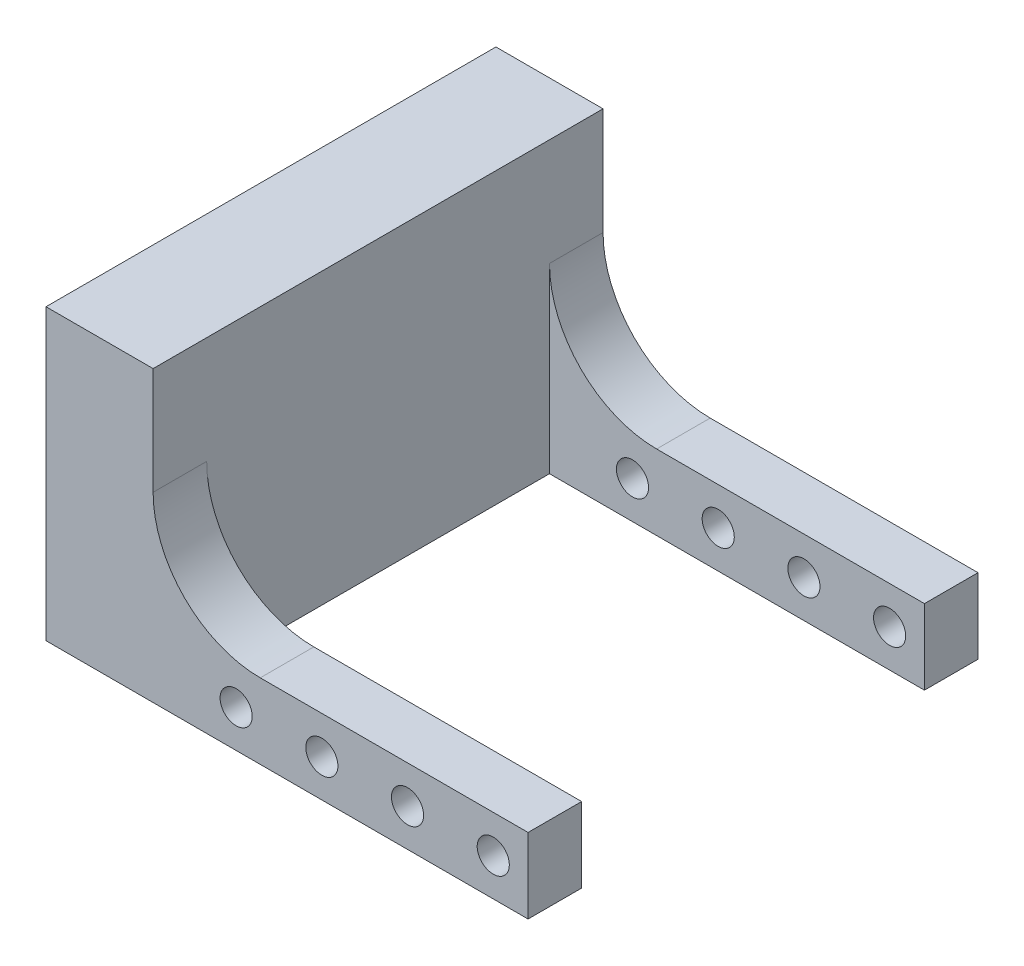
SolidWorks part; units mm, degrees
ref_plane "Plan de face" through (0, 0, 0) normal (0, 0, 1) x (1, 0, 0)
ref_plane "Plan de dessus" through (0, 0, 0) normal (0, 1, 0) x (1, 0, 0)
ref_plane "Plan de droite" through (0, 0, 0) normal (1, 0, 0) x (0, 0, -1)
sketch "Esquisse1" plane through (0, 0, 0) normal (0, 0, 1) x (1, 0, 0)
  line L0 (0, 7) -> (0, 27)
  line L1 (0, 0) -> (35, 0)
  line L2 (0, 0) -> (0, 7) construction
  line L3 (0, 7) -> (35, 7)
  line L4 (35, 0) -> (35, 7)
  line L5 (0, 0) -> (-10, 0)
  line L6 (0, 0) -> (0, 27) construction
  line L7 (0, 27) -> (-10, 27)
  line L8 (-10, 0) -> (-10, 27)
  dimension "D1" = 7
  dimension "D2" = 10
  dimension "D3" = 20
  dimension "D4" = 35
extrude "Boss.-Extru.1" add sketch "Esquisse1" along normal blind 42
sketch "Esquisse2" plane through (0, 0, 42) normal (0, 0, 1) x (1, 0, 0)
  line L0 (35, 3.5) -> (2.651, 3.5) construction
  line L1 (35, 0) -> (35, 7) construction
  line L2 (-10, 0) -> (35, 0) construction
  circle A0 centre (31.75, 3.5) radius 1.5
  circle A1 centre (23.75, 3.5) radius 1.5
  circle A2 centre (15.75, 3.5) radius 1.5
  circle A3 centre (7.75, 3.5) radius 1.5
  point P9 (0, 0)
  dimension "D4" = 35
  dimension "D2" = 3
  dimension "D1" = 3.5
  dimension "D3" = 7.75
sketch "Esquisse3" plane through (0, 7, 0) normal (0, 1, 0) x (1, 0, 0)
  line L0 (35, -42) -> (35, 0) construction
  line L1 (35, -37) -> (0, -37)
  line L2 (35, -37) -> (35, -5)
  line L3 (35, -5) -> (0, -5)
  line L4 (0, -37) -> (0, -5)
  line L5 (0, -42) -> (0, 0) construction
  line L6 (35, -42) -> (35, -37) construction
  line L7 (35, -5) -> (35, 0) construction
  dimension "D1" = 5
extrude "Enlèv. mat.-Extru.2" cut sketch "Esquisse3" against normal through all
extrude "Enlèv. mat.-Extru.3" cut sketch "Esquisse2" against normal through all
fillet "Congé1" radius 10 2 edges at (0, 7, 2.5) (0, 7, 39.5)
